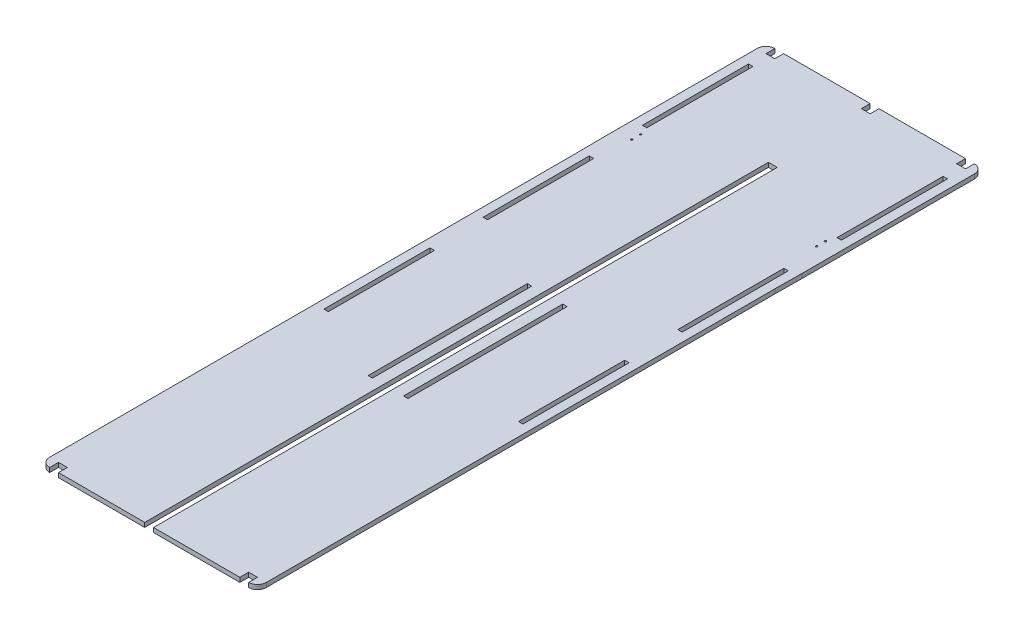
SolidWorks part; units mm, degrees
ref_plane "Front" through (0, 0, 0) normal (0, 0, 1) x (1, 0, 0)
ref_plane "Top" through (0, 0, 0) normal (0, 1, 0) x (1, 0, 0)
ref_plane "Right" through (0, 0, 0) normal (1, 0, 0) x (0, 0, -1)
sketch "Sketch2" plane through (0, 0, 0) normal (0, 1, 0) x (1, 0, 0)
  line L0 (122.5, 590) -> (122.5, -185) construction
  line L2 (0, 0) -> (0, 375)
  line L3 (0, 590) -> (245, 590)
  line L4 (245, -10) -> (245, 355)
  line L5 (10, 590) -> (10, -230) construction
  line L7 (117.5, -230) -> (117.5, 475)
  line L8 (117.5, 475) -> (127.5, 475)
  line L9 (127.5, -230) -> (127.5, 475)
  line L10 (117.5, -230) -> (127.5, 475) construction
  line L11 (117.5, 475) -> (127.5, -230) construction
  line L12 (10, -230) -> (15, -230)
  line L13 (15, -230) -> (15, 590) construction
  line L14 (235, 590) -> (235, -230) construction
  line L15 (235, -230) -> (230, -230)
  line L16 (230, -230) -> (230, 590) construction
  line L18 (0, 0) -> (0, -230)
  line L19 (245, -10) -> (245, -230)
  line L20 (0, -230) -> (117.5, -230)
  line L21 (127.5, -230) -> (245, -230)
  line L22 (-0.3, 405) -> (0, 375)
  line L23 (-0.3, 405) -> (-0.3, 590)
  line L24 (-0.3, 590) -> (0, 590)
  line L25 (10, 560) -> (15, 560)
  line L26 (245.3, 385) -> (245, 355)
  line L27 (245.3, 385) -> (245.3, 590)
  line L28 (245.3, 590) -> (245, 590)
  line L29 (10, 560) -> (10, 440)
  line L30 (10, 440) -> (15, 440)
  line L31 (15, 560) -> (15, 440)
  line L32 (15, 380) -> (10, 380)
  line L33 (15, 380) -> (15, 260)
  line L34 (15, 260) -> (10, 260)
  line L35 (10, 380) -> (10, 260)
  line L36 (10, 200) -> (15, 200)
  line L37 (10, 200) -> (10, 80)
  line L38 (10, 80) -> (15, 80)
  line L39 (15, 200) -> (15, 80)
  line L40 (230, 560) -> (235, 560)
  line L41 (230, 560) -> (230, 440)
  line L42 (230, 440) -> (235, 440)
  line L43 (235, 560) -> (235, 440)
  line L44 (230, 380) -> (235, 380)
  line L45 (230, 380) -> (230, 260)
  line L46 (230, 260) -> (235, 260)
  line L47 (235, 380) -> (235, 260)
  line L48 (230, 200) -> (235, 200)
  line L49 (230, 200) -> (230, 80)
  line L50 (230, 80) -> (235, 80)
  line L51 (235, 200) -> (235, 80)
  point P7 (122.5, 122.5)
  dimension "D1" = 245
  dimension "D2" = 820
  dimension "D3" = 115
  dimension "D4" = 10
  dimension "D5" = 590
  dimension "D6" = 10
  dimension "D7" = 5
  dimension "D8" = 10
  dimension "D9" = 5
  dimension "D10" = 30
  dimension "D11" = 120
  dimension "D12" = 60
  dimension "D13" = 0.3
  dimension "D14" = 30
  dimension "D15" = 30
  dimension "D16" = 120
  dimension "D17" = 60
  dimension "D18" = 120
  dimension "D19" = 120
  dimension "D20" = 60
  dimension "D21" = 120
  dimension "D22" = 60
  dimension "D23" = 120
extrude "Boss-Extrude1" add sketch "Sketch2" along normal blind 5 contours L4 L3 L2 L9 L7 L8 region at (8.5599, 0, -187.5)
sketch "Sketch3" plane through (0, 5, 0) normal (0, 1, 0) x (1, 0, 0)
  line L0 (18, 510.3998) -> (18, 370) construction
  line L1 (0, -230) -> (0, 375) construction
  line L2 (-0.3, 590) -> (245.3, 590) construction
  line L3 (117.5, 475) -> (127.5, 475) construction
  line L4 (105, 220) -> (100, 220)
  line L5 (105, 220) -> (105, 40)
  line L6 (105, 40) -> (100, 40)
  line L7 (100, 220) -> (100, 40)
  line L8 (117.5, -230) -> (117.5, 475) construction
  circle A0 centre (18, 410) radius 1 construction
  circle A1 centre (18, 420) radius 1
  circle A2 centre (18, 430) radius 1
  circle A3 centre (18, 440) radius 1 construction
  dimension "D7" = 2
  dimension "D8" = 2
  dimension "D9" = 2
  dimension "D10" = 2
  dimension "D1" = 18
  dimension "D2" = 220
  dimension "D3" = 40
  dimension "D4" = 10
  dimension "D5" = 10
  dimension "D6" = 10
  dimension "D11" = 5
  dimension "D12" = 255
  dimension "D13" = 12.5
  dimension "D14" = 180
extrude "Cut-Extrude1" cut sketch "Sketch3" against normal blind 5
ref_plane "Plane1" through (122.5, 0, 0) normal (-1, 0, 0) x (0, 0, 1)
mirror "Mirror1" about plane through (122.5, 0, 0) normal (-1, 0, 0) of "Cut-Extrude1"
fillet "Fillet1" radius 10 4 edges at (245.3, 2.5, -590) (-0.3, 2.5, -590) (0, 2.5, 230) (245, 2.5, 230)
sketch "Sketch4" plane through (0, 5, 0) normal (0, 1, 0) x (1, 0, 0)
  line L0 (235.3, 590) -> (9.7, 590) construction
  line L1 (10, -230) -> (20, -230)
  line L2 (10, -230) -> (10, -220)
  line L3 (10, -220) -> (20, -220)
  line L4 (20, -230) -> (20, -220)
  line L5 (235, -230) -> (225, -230)
  line L6 (235, -230) -> (235, -220)
  line L7 (235, -220) -> (225, -220)
  line L8 (225, -230) -> (225, -220)
  line L9 (9.7, 590) -> (19.7, 590)
  line L10 (9.7, 590) -> (9.7, 580)
  line L11 (9.7, 580) -> (19.7, 580)
  line L12 (19.7, 590) -> (19.7, 580)
  line L13 (235.3, 590) -> (225.3, 590)
  line L14 (235.3, 590) -> (235.3, 580)
  line L15 (235.3, 580) -> (225.3, 580)
  line L16 (225.3, 590) -> (225.3, 580)
  line L17 (117.5, 590) -> (127.5, 590)
  line L18 (117.5, 590) -> (117.5, 580)
  line L19 (117.5, 580) -> (127.5, 580)
  line L20 (127.5, 590) -> (127.5, 580)
  point P26 (122.5, 590)
  point P27 (122.5, 590)
  dimension "D1" = 10
  dimension "D2" = 10
  dimension "D3" = 10
  dimension "D4" = 10
  dimension "D5" = 10
  dimension "D6" = 10
  dimension "D7" = 10
  dimension "D8" = 10
  dimension "D9" = 10
  dimension "D10" = 10
extrude "Cut-Extrude2" cut sketch "Sketch4" against normal blind 10
